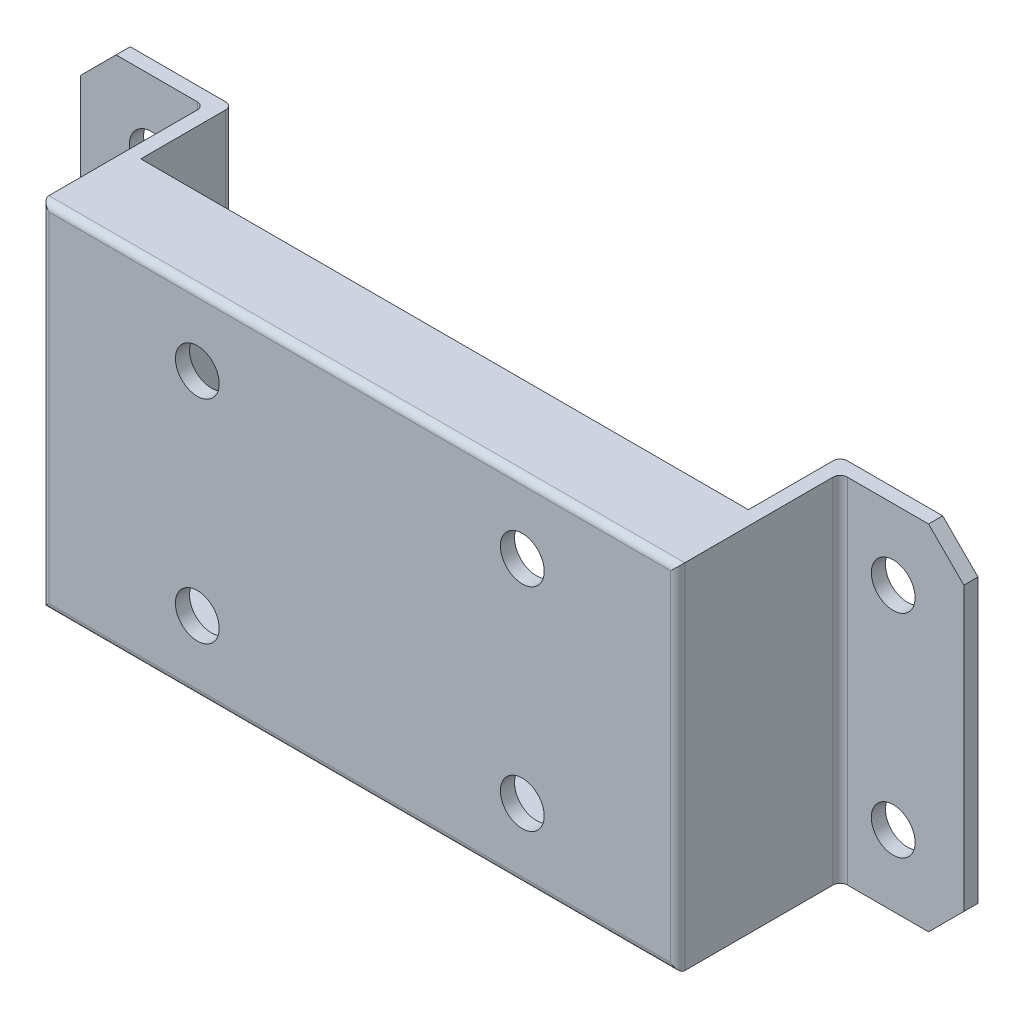
SolidWorks part; units mm, degrees
note: The reader was unsure of these and kept them because the rebuilt part matched: shared geometry of "草图5<3>".
ref_plane "前视基准面" through (0, 0, 0) normal (0, 0, 1) x (1, 0, 0)
ref_plane "上视基准面" through (0, 0, 0) normal (0, 1, 0) x (1, 0, 0)
ref_plane "右视基准面" through (0, 0, 0) normal (1, 0, 0) x (0, 0, -1)
sketch "草图1" plane through (0, 0, 0) normal (0, 0, 1) x (1, 0, 0)
  line L0 (-124.611, 0) -> (144.5186, 0) construction
  line L1 (0, 101.4276) -> (0, -103.6955) construction
  line L2 (0, -103.6955) -> (1.134, -103.6955) construction
  line L4 (-45, 25) -> (45, 25)
  line L5 (-45, 25) -> (-45, -25)
  line L6 (-45, -25) -> (45, -25)
  line L7 (45, 25) -> (45, -25)
  dimension "D1" = 90
  dimension "D2" = 50
sheet metal parameters "钣金1" thickness 2 parameters "D1"=0.7366
base flange "基体-法兰1" sketch "草图1" thickness 2 reverse thickness direction no parameters "D1"=0.7366
sketch "草图5" plane through (0, 0, -2) normal (0, 0, -1) x (-1, 0, 0)
  line L0 (45, -25) -> (-45, -25) construction
  line L1 (-45, 25) -> (-43, 25)
  line L2 (-45, 25) -> (-45, -25)
  line L3 (-45, -25) -> (-43, -25)
  line L4 (-43, 25) -> (-43, -25)
  line L6 (45, 25) -> (43, 25)
  line L7 (45, 25) -> (45, -25)
  line L8 (45, -25) -> (43, -25)
  line L9 (43, 25) -> (43, -25)
  line L10 (-43, 23) -> (43, 23)
  line L11 (-43, 23) -> (-43, 25)
  line L12 (-43, 25) -> (43, 25)
  line L13 (43, 23) -> (43, 25)
  line L14 (-43, -25) -> (43, -25)
  line L15 (-43, -25) -> (-43, -23)
  line L16 (-43, -23) -> (43, -23)
  line L17 (43, -25) -> (43, -23)
  line M1 (45, -25) -> (45, 25)
  line M2 (45, 25) -> (-45, 25)
  line M3 (-45, 25) -> (-45, -25)
  line M4 (-45, -25) -> (45, -25)
  dimension "D1" = 2
  dimension "D2" = 2
  dimension "D3" = 2
  dimension "D4" = 2
extrude "凸台-拉伸1" add sketch "草图5" along normal blind 23 contours L4 M2 M3 M4 | L9 M2 M4 M1
extrude "凸台-拉伸2" add sketch "草图5<3>" along normal blind 10 contours L4 L10 L9 M2 | L16 L4 L9 M4
sketch "草图5<3>" plane through (0, 0, -2) normal (0, 0, -1) x (-1, 0, 0) same geometry as "草图5"
sketch "草图10" plane through (-45, 0, 0) normal (-1, 0, 0) x (0, 0, 1)
  line L0 (-25, -25) -> (0, -25) construction
  line L1 (-25, 25) -> (-23, 25)
  line L2 (-25, 25) -> (-25, -25)
  line L3 (-25, -25) -> (-23, -25)
  line L4 (-23, 25) -> (-23, -25)
  dimension "D1" = 2
extrude "凸台-拉伸3" add sketch "草图10" along normal blind 17.5
sketch "草图11" plane through (0, 0, -25) normal (0, 0, -1) x (-1, 0, 0)
  line L0 (57.5, 25) -> (62.5, 20)
  line L1 (62.5, 25) -> (43, 25) construction
  line L2 (62.5, 25) -> (62.5, -25) construction
  line L3 (57.5, -25) -> (62.5, -20)
  line L4 (43, -25) -> (62.5, -25) construction
  line L5 (62.5, -20) -> (62.5, -25)
  line L6 (62.5, -25) -> (57.5, -25)
  line L7 (57.5, 25) -> (62.5, 25)
  line L8 (62.5, 25) -> (62.5, 20)
  dimension "D1" = 5
  dimension "D2" = 5
  dimension "D3" = 5
  dimension "D4" = 5
extrude "切除-拉伸1" cut sketch "草图11" against normal through all
mirror "镜向3" about plane through (0, 0, 0) normal (1, 0, 0) of "切除-拉伸1", "凸台-拉伸3"
fillet "圆角1" radius 1 18 edges at (-43, 0, -25) (-43, 0, -2) (0, 23, -2) (0, -23, -2) (0, 25, 0) (45, 0, 0) (0, -25, 0) (-45, 0, 0) (43, 0, -25)
sketch "草图12" plane through (0, 0, -25) normal (0, 0, -1) x (-1, 0, 0)
  line L0 (-62.5, 20) -> (-62.5, -20) construction
  line L1 (-44, 25) -> (-57.5, 25) construction
  circle A0 centre (-52.5, 15) radius 3.1
  dimension "D3" = 6.2
  dimension "D1" = 10
  dimension "D2" = 10
extrude "切除-拉伸2" cut sketch "草图12" against normal through all
sketch "草图13" plane through (0, 0, 0) normal (0, 0, 1) x (1, 0, 0)
  line L0 (-45, 25) -> (45, 25) construction
  line L1 (45, 25) -> (45, -25) construction
  circle A0 centre (23, 15) radius 3.1
  dimension "D3" = 6.2
  dimension "D1" = 10
  dimension "D2" = 22
extrude "切除-拉伸3" cut sketch "草图13" against normal through all
mirror "镜向4" about plane through (0, 0, 0) normal (0, 1, 0) of "切除-拉伸3", "切除-拉伸2"
mirror "镜向5" about plane through (0, 0, 0) normal (1, 0, 0) of "镜向4", "切除-拉伸2", "切除-拉伸3"
flat pattern "平板型式1" [suppressed]
sketch "折弯-线1" plane through (0, 0, 0) normal (0, 1, 0) x (-1, 0, 0)
sketch3d "边界框1" [suppressed]
  line L0 (0, 0, 0) -> (-90, 0, 0) construction
  line L1 (0, 50, 0) -> (-90, 50, 0) construction
  line L2 (0, 0, 0) -> (0, 50, 0) construction
  line L3 (-90, 0, 0) -> (-90, 50, 0) construction
